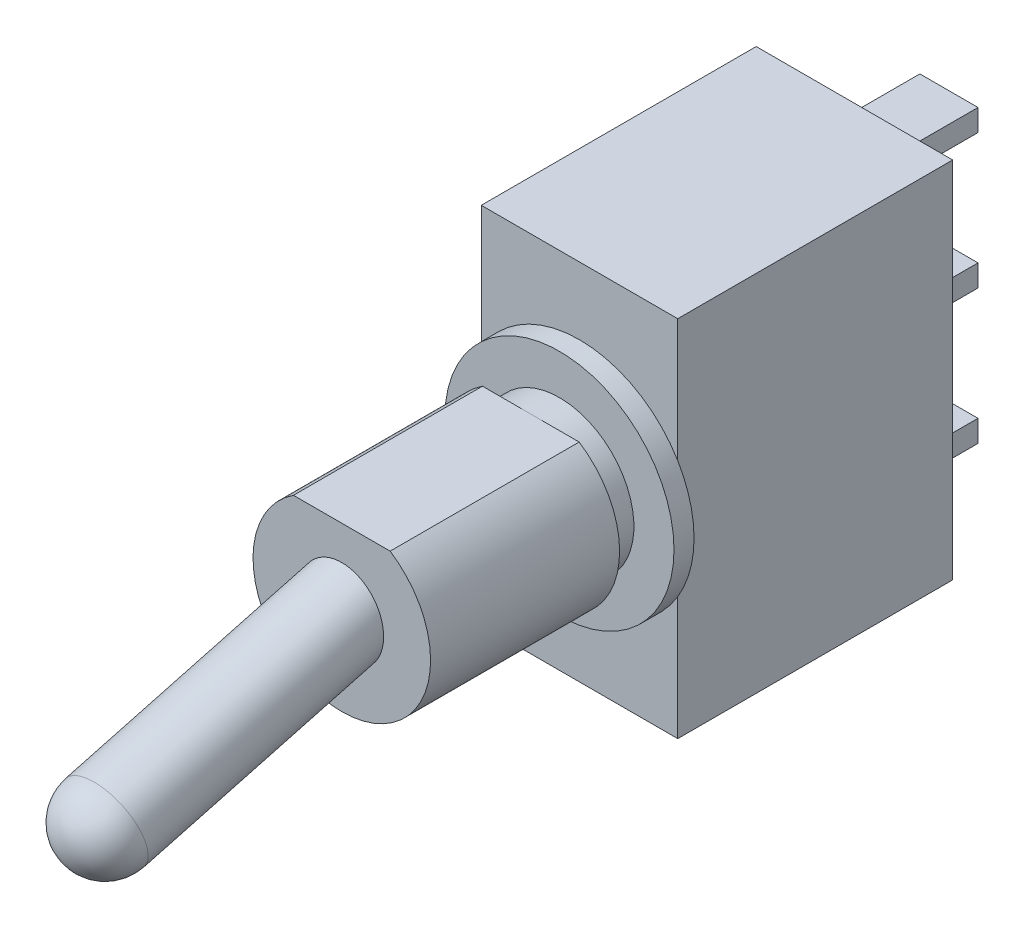
SolidWorks part; units mm, degrees
ref_plane "Plan de face" through (0, 0, 0) normal (0, 0, 1) x (1, 0, 0)
ref_plane "Plan de dessus" through (0, 0, 0) normal (0, 1, 0) x (1, 0, 0)
ref_plane "Plan de droite" through (0, 0, 0) normal (1, 0, 0) x (0, 0, -1)
sketch "Esquisse1" plane through (0, 0, 0) normal (0, 0, 1) x (1, 0, 0)
  line L1 (-3.43, 6.35) -> (3.43, 6.35)
  line L2 (-3.43, 6.35) -> (-3.43, -6.35)
  line L3 (-3.43, -6.35) -> (3.43, -6.35)
  line L4 (3.43, 6.35) -> (3.43, -6.35)
  line L5 (-3.43, 6.35) -> (3.43, -6.35) construction
  line L6 (-3.43, -6.35) -> (3.43, 6.35) construction
  point P0 (0, 0)
  dimension "D1" = 12.7
  dimension "D2" = 6.86
extrude "Boss.-Extru.1" add sketch "Esquisse1" along normal blind 9.6
sketch "Sketch1" plane through (0, 0, 9.6) normal (0, 0, -1) x (-1, 0, 0)
  circle A0 centre (0, 0) radius 4
  dimension "D1" = 8
extrude "Boss-Extrude1" add sketch "Sketch1" against normal blind 0.7
sketch "Sketch2" plane through (0, 0, 0) normal (1, 0, 0) x (0, 0, -1)
  line L0 (0, 0) -> (-24.5076, 0) construction
  line L1 (-10.3, 2.6) -> (-11.3, 2.6)
  line L2 (-10.3, 4) -> (-10.3, -4) construction
  line L3 (-11.3, 2.6) -> (-11.3, 3.1)
  line L4 (-11.3, 3.1) -> (-17.9, 3.1)
  line L5 (-17.9, 3.1) -> (-17.9, 0)
  line L6 (-17.9, 0) -> (-10.3, 0)
  line L7 (-10.3, 0) -> (-10.3, 2.6)
  dimension "D1" = 5.2
  dimension "D2" = 6.2
  dimension "D3" = 7.6
  dimension "D4" = 1
revolve "Revolve1" add sketch "Sketch2" angle 360 about L0
sketch "Esquisse3" plane through (0, 0, 0) normal (1, 0, 0) x (0, 0, -1)
  line L0 (-17.5221, 0) -> (-38.709, -5.677) construction
  line L1 (-17.9, 3.1) -> (-17.9, -3.1) construction
  line L2 (0, 0) -> (-25.0079, 0) construction
  line L3 (-26.545, -0.9062) -> (-17.9, 1.4103)
  line L4 (-17.9, 1.4103) -> (-17.5221, 0)
  line L5 (-17.5221, 0) -> (-27.5774, -2.6943)
  arc A0 (-27.5774, -2.6943) -> (-26.545, -0.9062) centre (-26.1672, -2.3164) cw
  point P0 (0, 0)
  dimension "D1" = 15
  dimension "D2" = 2.92
  dimension "D3" = 10.41
revolve "Révolution1" add sketch "Esquisse3" angle 360 about L0
sketch "Esquisse4" plane through (0, 0, 0) normal (0, 0, 1) x (1, 0, 0)
  line L1 (-1.015, 0.38) -> (1.015, 0.38)
  line L2 (-1.015, 0.38) -> (-1.015, -0.38)
  line L3 (-1.015, -0.38) -> (1.015, -0.38)
  line L4 (1.015, 0.38) -> (1.015, -0.38)
  line L5 (-1.015, 0.38) -> (1.015, -0.38) construction
  line L6 (-1.015, -0.38) -> (1.015, 0.38) construction
  line L7 (-1.015, 5.08) -> (1.015, 5.08)
  line L8 (-1.015, 5.08) -> (-1.015, 4.32)
  line L9 (-1.015, 4.32) -> (1.015, 4.32)
  line L10 (1.015, 5.08) -> (1.015, 4.32)
  line L11 (-1.015, 5.08) -> (1.015, 4.32) construction
  line L12 (-1.015, 4.32) -> (1.015, 5.08) construction
  line L13 (-1.015, -4.32) -> (1.015, -4.32)
  line L14 (-1.015, -4.32) -> (-1.015, -5.08)
  line L15 (-1.015, -5.08) -> (1.015, -5.08)
  line L16 (1.015, -4.32) -> (1.015, -5.08)
  line L17 (-1.015, -4.32) -> (1.015, -5.08) construction
  line L18 (-1.015, -5.08) -> (1.015, -4.32) construction
  point P0 (0, 0)
  point P5 (0, 4.7)
  point P11 (0, -4.7)
  dimension "D1" = 0.76
  dimension "D2" = 2.03
  dimension "D3" = 0.76
  dimension "D4" = 2.03
  dimension "D5" = 0.76
  dimension "D6" = 2.03
  dimension "D7" = 4.7
  dimension "D8" = 4.7
extrude "Boss.-Extru.3" add sketch "Esquisse4" against normal blind 3.3
sketch "Sketch3" plane through (0, 0, 17.9) normal (0, 0, 1) x (1, 0, 0)
  line L1 (-3.1839, 2.6) -> (3.6492, 2.6)
  line L2 (-3.1839, 2.6) -> (-3.1839, 5.5022)
  line L3 (-3.1839, 5.5022) -> (3.6492, 5.5022)
  line L4 (3.6492, 2.6) -> (3.6492, 5.5022)
  circle A0 centre (0, 0) radius 2.6 construction
extrude "Cut-Extrude1" cut sketch "Sketch3" against normal up to surface (7.6 mm away) up to face at (-2.6, 0, 10.3)
